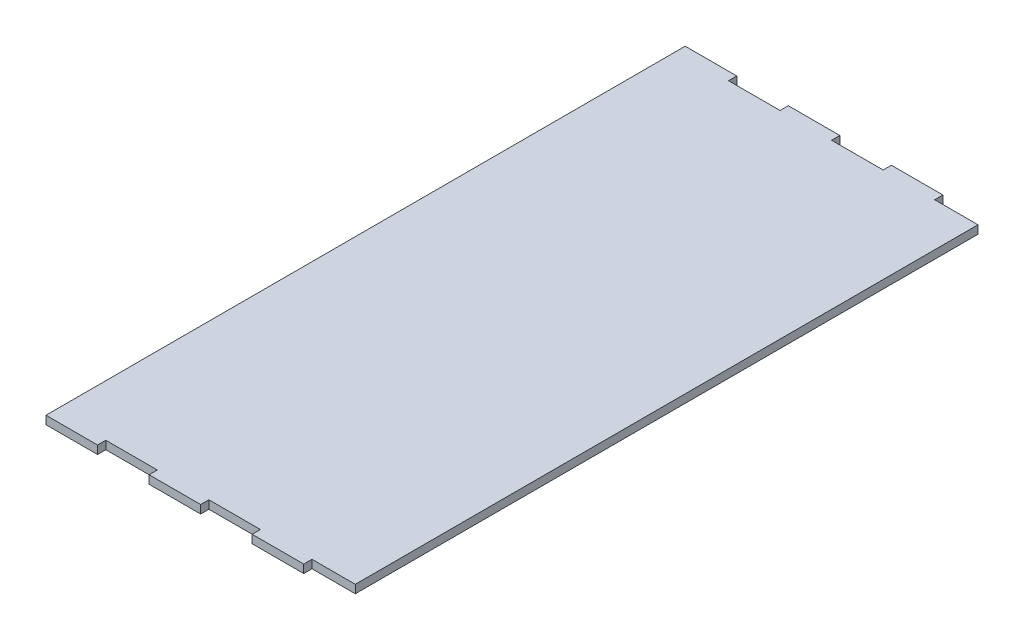
SolidWorks part; units mm, degrees
ref_plane "Alzado" through (0, 0, 0) normal (0, 0, 1) x (1, 0, 0)
ref_plane "Planta" through (0, 0, 0) normal (0, 1, 0) x (1, 0, 0)
ref_plane "Vista lateral" through (0, 0, 0) normal (1, 0, 0) x (0, 0, -1)
sketch "Croquis1" plane through (0, 0, 0) normal (0, 1, 0) x (1, 0, 0)
  line L0 (-100, 155) -> (-50, 155)
  line L1 (-200, 155) -> (200, 155) construction
  line L2 (-200, 155) -> (-200, -155) construction
  line L3 (-200, -155) -> (200, -155) construction
  line L4 (200, 155) -> (200, -155) construction
  line L5 (-200, 155) -> (200, -155) construction
  line L6 (-200, -155) -> (200, 155) construction
  line L7 (-200, -155) -> (-150, -155)
  line L8 (-200, -155) -> (-200, 155)
  line L9 (-200, 155) -> (-150, 155)
  line L10 (-50, -155) -> (-50, 155)
  line L11 (-150, -151) -> (-100, -151) construction
  line L12 (-150, -151) -> (-150, -155) construction
  line L13 (-150, -155) -> (-100, -155) construction
  line L14 (-100, -151) -> (-100, -155) construction
  line L15 (-150, 151) -> (-100, 151) construction
  line L16 (-150, 151) -> (-150, 155) construction
  line L17 (-150, 155) -> (-100, 155) construction
  line L18 (-100, 151) -> (-100, 155) construction
  line L19 (-150, 151) -> (-100, 155) construction
  line L20 (-150, 155) -> (-100, 151) construction
  line L21 (-200, 105) -> (-196, 105) construction
  line L22 (-200, 105) -> (-200, 55) construction
  line L23 (-200, 55) -> (-196, 55) construction
  line L24 (-196, 105) -> (-196, 55) construction
  line L25 (-200, 105) -> (-196, 55) construction
  line L26 (-200, 55) -> (-196, 105) construction
  line L27 (-200, -55) -> (-196, -55) construction
  line L28 (-200, -55) -> (-200, -105) construction
  line L29 (-200, -105) -> (-196, -105) construction
  line L30 (-196, -55) -> (-196, -105) construction
  line L31 (-200, -55) -> (-196, -105) construction
  line L32 (-200, -105) -> (-196, -55) construction
  line L33 (-100, -155) -> (-50, -155)
  line L34 (-196, 155) -> (-196, -155)
  line L35 (-150, 155) -> (-100, 155)
  line L36 (-150, -155) -> (-100, -155)
  point P0 (0, 0)
  point P16 (-125, 153)
  point P21 (-198, 80)
  point P26 (-198, -80)
  point P30 (-196, -105)
  dimension "D1" = 310
  dimension "D2" = 400
  dimension "D3" = 150
  dimension "D4" = 50
  dimension "D5" = 50
  dimension "D6" = 50
  dimension "D7" = 50
  dimension "D8" = 50
  dimension "D9" = 4
extrude "Saliente-Extruir1" add sketch "Croquis1" along normal blind 4 contours L9 L34 L7 L12 L11 L14 L33 L10 L0 L18 L15 L16 region at (-123, 0, 0)
sketch "Croquis2" plane through (0, 4, 0) normal (0, 1, 0) x (1, 0, 0)
  line L0 (-196, 155) -> (-171, 155)
  line L1 (-196, 155) -> (-50, 155) construction
  line L2 (-171, 155) -> (-171, 151)
  line L3 (-171, 151) -> (-146, 151)
  line L4 (-146, 151) -> (-146, 155)
  line L5 (-146, 155) -> (-121, 155)
  line L6 (-121, 155) -> (-121, 151)
  line L7 (-121, 151) -> (-96, 151)
  line L8 (-96, 151) -> (-96, 155)
  line L9 (-96, 155) -> (-71, 155)
  line L10 (-71, 155) -> (-71, 151)
  line L11 (-71, 151) -> (-46, 151)
  line L12 (-46, 151) -> (-46, 195.5944)
  line L13 (-46, 195.5944) -> (-196, 195.5944)
  line L14 (-196, 195.5944) -> (-196, 155)
  line L15 (-2.2, 0) -> (2.2, 0) construction
  line L16 (-196, -195.5944) -> (-196, -155)
  line L17 (-46, -195.5944) -> (-196, -195.5944)
  line L18 (-46, -151) -> (-46, -195.5944)
  line L19 (-71, -151) -> (-46, -151)
  line L20 (-71, -155) -> (-71, -151)
  line L21 (-96, -155) -> (-71, -155)
  line L22 (-96, -151) -> (-96, -155)
  line L23 (-121, -151) -> (-96, -151)
  line L24 (-121, -155) -> (-121, -151)
  line L25 (-146, -155) -> (-121, -155)
  line L26 (-146, -151) -> (-146, -155)
  line L27 (-171, -151) -> (-146, -151)
  line L28 (-171, -155) -> (-171, -151)
  line L29 (-196, -155) -> (-171, -155)
  point P5 (0, 155)
  dimension "D1" = 25
  dimension "D2" = 4
extrude "Cortar-Extruir1" cut sketch "Croquis2" against normal blind 10
equation "\"D2@Croquis1\" = \"largo_tot\""
equation "\"D3@Croquis1\"=150"
equation "\"D1@Croquis1\" = \"ancho_tot\""
equation "\"venesta\"= 4'grosor de la venesta"
equation "\"policarbonato\"= 4'grosor del policarbonato"
equation "\"carton_trupan\"= 3'grosor del carton trupan caso laser"
equation "\"ancho_tot\"= 310'ancho tot sin llantas"
equation "\"largo_tot\"= 400'largo tot sin camera"
equation "\"D1@Saliente-Extruir1\"=\"policarbonato\""
equation "\"D9@Croquis1\"=\"policarbonato\""
equation "\"D2@Croquis2\"=\"policarbonato\""
